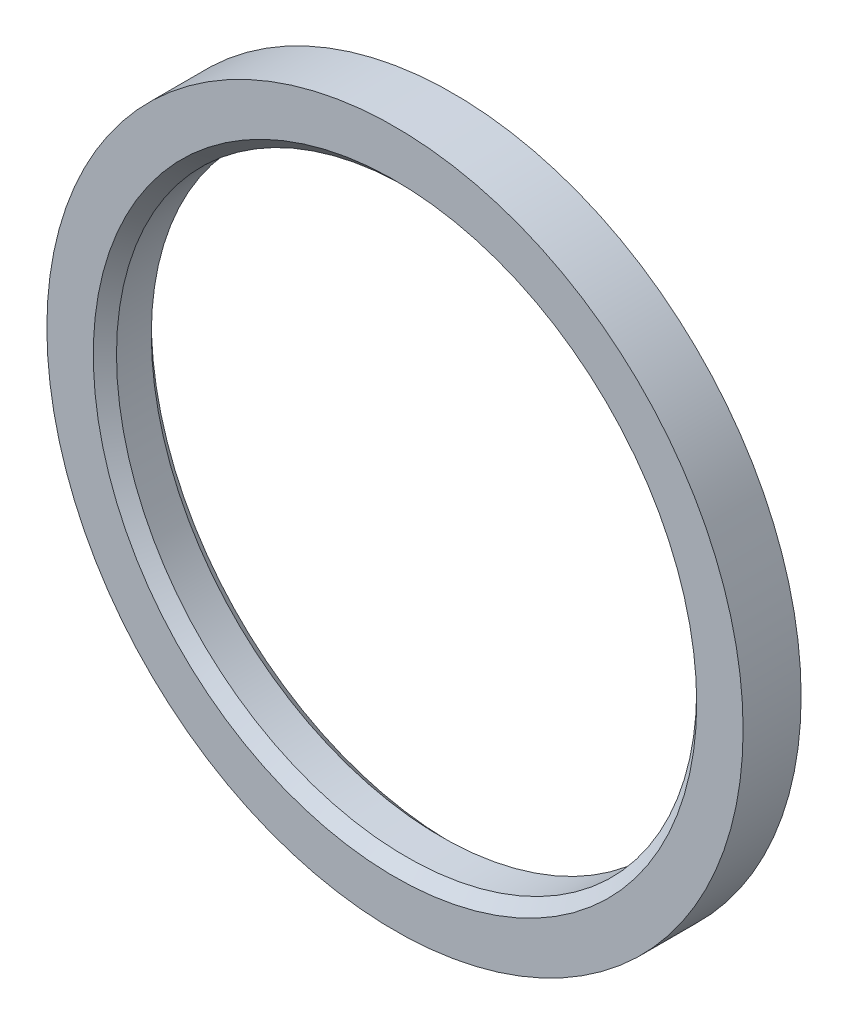
SolidWorks part; units mm, degrees
material "6061 合金"
ref_plane "前视基准面" through (0, 0, 0) normal (0, 0, 1) x (1, 0, 0)
ref_plane "上视基准面" through (0, 0, 0) normal (0, 1, 0) x (1, 0, 0)
ref_plane "右视基准面" through (0, 0, 0) normal (1, 0, 0) x (0, 0, -1)
other "Configuration Table"
sketch "草图1" plane through (0, 0, 0) normal (0, 0, 1) x (1, 0, 0)
  circle A0 centre (0, 0) radius 5
  circle A1 centre (0, 0) radius 6
  dimension "D1" = 10
  dimension "D2" = 12
extrude "凸台-拉伸1" add sketch "草图1" along normal blind 1 contours A0 | A1 region at (0, 0, 0)
sketch "草图2" plane through (0, 0, 0) normal (0, 0, -1) x (-1, 0, 0)
  circle A0 centre (0, 0) radius 7
  circle A1 centre (0, 0) radius 5 construction
  circle A2 centre (0, 0) radius 5
  dimension "D1" = 14
extrude "凸台-拉伸2" [suppressed] add sketch "草图2" against normal blind 1
sketch "草图3" [suppressed] plane through (0, 0, 15) normal (0, 0, 1) x (1, 0, 0)
  circle A1 centre (0, 0) radius 5 construction
  circle A2 centre (0, 0) radius 5
  circle A3 centre (0, 0) radius 7 construction
  circle A4 centre (0, 0) radius 7
extrude "凸台-拉伸3" [suppressed] add sketch "草图3" against normal blind 1
fillet "圆角1" [suppressed] radius 0.5
chamfer "倒角1" distance 0.2 angle 45 2 edges at (5, 0, 0) (5, 0, 1)
